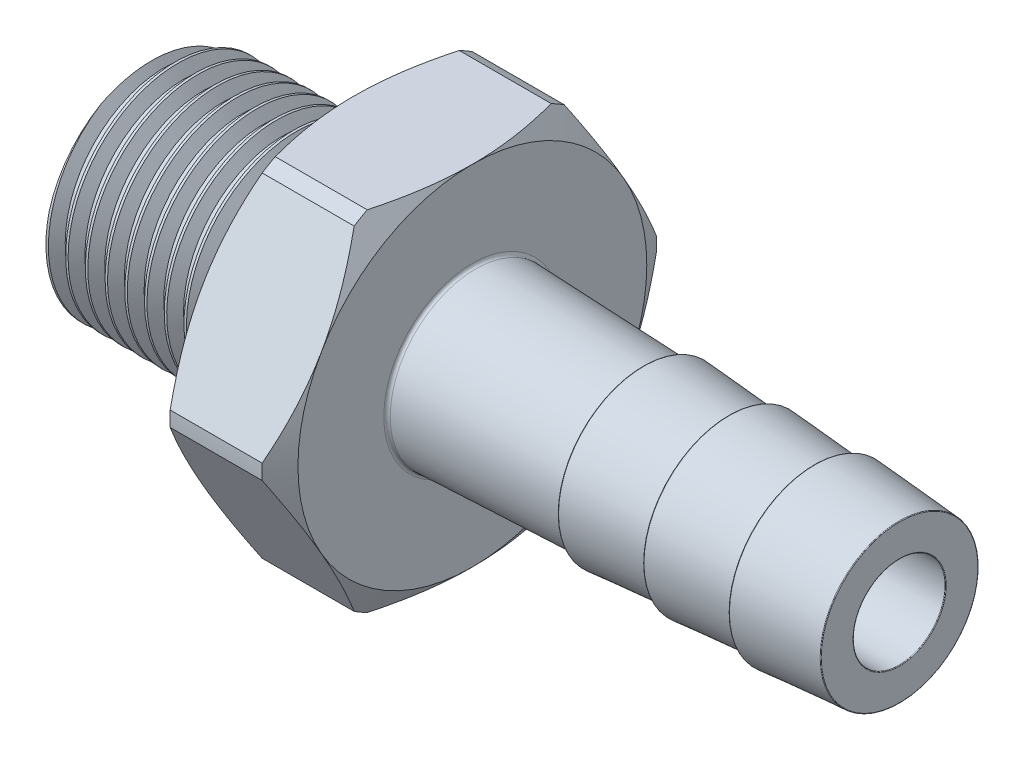
SolidWorks part; units mm, degrees
ref_plane "Front Plane" through (0, 0, 0) normal (0, 0, 1) x (1, 0, 0)
ref_plane "Top Plane" through (0, 0, 0) normal (0, 1, 0) x (1, 0, 0)
ref_plane "Right Plane" through (0, 0, 0) normal (1, 0, 0) x (0, 0, -1)
sketch "Sketch1" plane through (0, 0, 0) normal (0, 1, 0) x (1, 0, 0)
  line L0 (0, 47.8903) -> (0, -41.9306) construction
  line L1 (-23.9296, 0) -> (108.5465, 0) construction
  line L2 (19, 3.5) -> (19, 6.5)
  line L3 (19, 6.5) -> (15, 6.5)
  line L4 (15, 6.5) -> (15, 13.2679)
  line L5 (16, 15) -> (23, 15)
  line L6 (24, 13.2679) -> (24, 6.5)
  line L7 (24, 6.5) -> (76.9453, 6.5) construction
  line L8 (24, 6) -> (76.9453, 6) construction
  line L9 (24, 6.5) -> (36.9481, 6.002)
  line L10 (37, 6.052) -> (37, 6.446)
  line L11 (37.0538, 6.4959) -> (43.4462, 6.0041)
  line L12 (43.5, 6.054) -> (43.5, 6.446)
  line L13 (43.5538, 6.4959) -> (49.9462, 6.0041)
  line L14 (50, 6.054) -> (50, 6.446)
  line L15 (50.0538, 6.4959) -> (56.4538, 6.0036)
  line L16 (56.5, 5.9537) -> (56.5, 3.5)
  line L17 (56.5, 3.5) -> (19, 3.5)
  line L18 (15, 6.5) -> (0, 6.5) construction
  line L19 (0, 6.5) -> (0, 8.5) construction
  line L20 (0, 8.5) -> (15, 8.5) construction
  line L21 (23, 15) -> (24, 13.2679)
  line L22 (15, 13.2679) -> (16, 15)
  arc A0 (56.4538, 6.0036) -> (56.5, 5.9537) centre (56.45, 5.9537) cw
  arc A1 (50, 6.446) -> (50.0538, 6.4959) centre (50.05, 6.446) cw
  arc A2 (49.9462, 6.0041) -> (50, 6.054) centre (49.95, 6.054) ccw
  arc A3 (43.5, 6.446) -> (43.5538, 6.4959) centre (43.55, 6.446) cw
  arc A4 (43.4462, 6.0041) -> (43.5, 6.054) centre (43.45, 6.054) ccw
  arc A5 (37, 6.446) -> (37.0538, 6.4959) centre (37.05, 6.446) cw
  arc A6 (36.9481, 6.002) -> (37, 6.052) centre (36.95, 6.052) ccw
  point P9 (15, 15)
  point P10 (24, 15)
  point P27 (56.5, 6)
  point P30 (50, 6.5)
  point P33 (50, 6)
  point P36 (43.5, 6.5)
  point P39 (43.5, 6)
  point P42 (37, 6.5)
  point P45 (37, 6)
  point P50 (0, 0)
  point P51 (0, 0)
  point P52 (0, 0)
  dimension "D13" = 0.05
  dimension "D2" = 15
  dimension "D3" = 2
  dimension "D4" = 19
  dimension "D5" = 3.5
  dimension "D6" = 56.5
  dimension "D7" = 32.5
  dimension "D8" = 8.5
  dimension "D9" = 6.5
  dimension "D10" = 6.5
  dimension "D11" = 6.5
  dimension "D12" = 15
  dimension "D14" = 1
  dimension "D15" = 30
  dimension "D16" = 30
  dimension "D17" = 1
  dimension "D18" = 120
  dimension "D1" = 0.5
revolve "Revolve1" add sketch "Sketch1" angle 360 about L1
sketch "Sketch2" plane through (0, 0, 0) normal (0, 1, 0) x (1, 0, 0)
  line L0 (15, 8.5) -> (15, 6.5)
  line L1 (15, 6.5) -> (0, 6.5)
  line L2 (15, 6.5) -> (0, 6.5) construction
  line L3 (0, 8.5) -> (15, 8.5)
  line L4 (0, 8.5) -> (15, 8.5) construction
  line L5 (0, 6.5) -> (0, 8.5)
revolve "Revolve2" add sketch "Sketch2" angle 360 about L1
thread "Thread1" pitch 1.5 method cut profile "Thread Profile1" start angle 0, offset 2, length 0, pitch 1.5, diameter 17
ref_plane "Plane1" through (-2, 0, -8.5) normal (0, -1, 0) x (0, 0, -1)
sketch "Thread Profile1" plane through (-2, 0, -8.5) normal (0, -1, 0) x (0, 0, -1)
  line L0 (0, 0) -> (0, 1.5) construction
  line L11 (0, 0) -> (0, 1.3125)
  line L12 (0, 1.3125) -> (-0.8119, 0.8437)
  line L13 (-0.8119, 0.8437) -> (-0.8119, 0.4687)
  line L15 (-0.8119, 0.4687) -> (0, 0)
  line L17 (-0.8119, 0.6562) -> (0, 0.6562) construction
  point P2 (0, 0)
  dimension "Pitch" = 1.5
  dimension "Profile_Angle" = 60
  dimension "Profile_Land" = 0.375
  dimension "Profile_Height" = 0.8119
sketch "Sketch5" plane through (24, 0, 0) normal (1, 0, 0) x (0, 0, -1)
  line L1 (-7.6603, 13.2679) -> (-15.3205, 0)
  line L2 (-15.3205, 0) -> (-7.6603, -13.2679)
  line L3 (-7.6603, -13.2679) -> (7.6603, -13.2679)
  line L4 (7.6603, -13.2679) -> (15.3205, 0)
  line L5 (15.3205, 0) -> (7.6603, 13.2679)
  line L6 (7.6603, 13.2679) -> (-7.6603, 13.2679)
  circle A0 centre (0, 0) radius 13.2679 construction
  circle A1 centre (0, 0) radius 13.2679 construction
extrude "Cut-Extrude1" cut sketch "Sketch5" against normal through all flip side to cut
fillet "Fillet1" radius 0.05 1 edges at (56.5, 0, 3.5)
fillet "Fillet2" radius 0.25 2 edges at (24, 0, 6.5) (19, 0, 6.5)
chamfer "Chamfer1" distance 2.5 angle 45 1 edges at (19, 0, 3.5)
